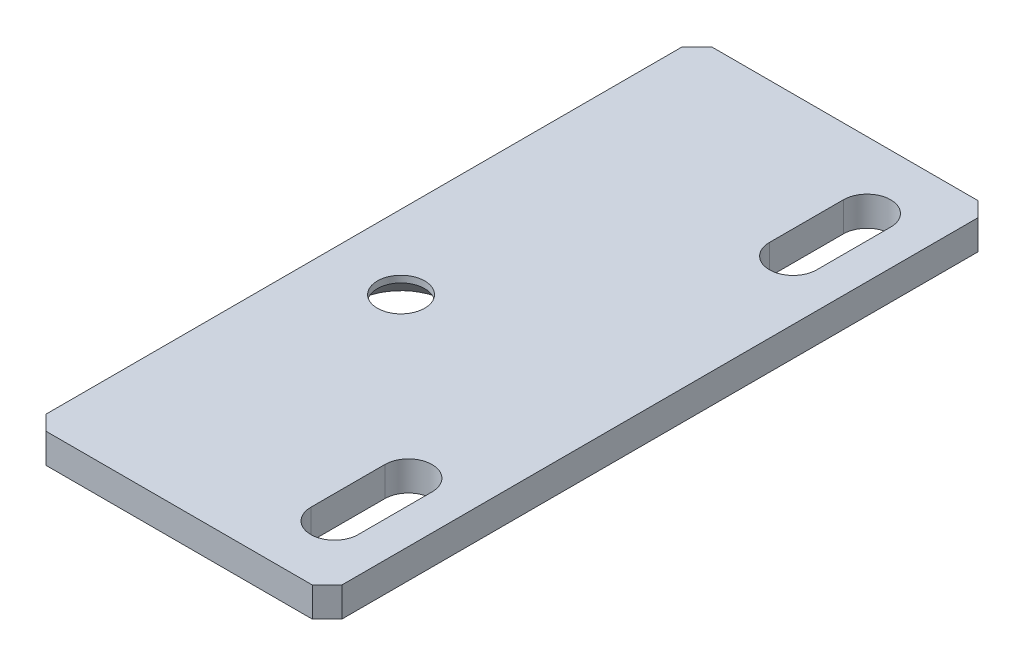
SolidWorks part; units mm, degrees
material "6061 Alloy"
ref_plane "Front Plane" through (0, 0, 0) normal (0, 0, 1) x (1, 0, 0)
ref_plane "Top Plane" through (0, 0, 0) normal (0, 1, 0) x (1, 0, 0)
ref_plane "Right Plane" through (0, 0, 0) normal (1, 0, 0) x (0, 0, -1)
sketch "Sketch1" plane through (0, 0, 0) normal (0, 1, 0) x (1, 0, 0)
  line L5 (10, -22.5) -> (-10, -22.5)
  line L6 (10, -22.5) -> (10, 22.5)
  line L7 (10, 22.5) -> (-10, 22.5)
  line L8 (-10, -22.5) -> (-10, 22.5)
  line L9 (10, -22.5) -> (-10, 22.5) construction
  line L10 (10, 22.5) -> (-10, -22.5) construction
  point P0 (0, 0)
  dimension "D3" = 20
  dimension "D4" = 45
extrude "Base" add sketch "Sketch1" along normal blind 2
sketch "Sketch6" plane through (0, 2, 0) normal (0, 1, 0) x (1, 0, 0)
  line L0 (6, 18) -> (6, 13) construction
  line L1 (7.6, 18) -> (7.6, 13)
  line L2 (4.4, 18) -> (4.4, 13)
  line L3 (6, -13) -> (6, -18) construction
  line L4 (7.6, -13) -> (7.6, -18)
  line L5 (4.4, -13) -> (4.4, -18)
  line L6 (0, 0) -> (-4.8321, 0) construction
  line L7 (10, -22.5) -> (10, 22.5) construction
  line L8 (10, 22.5) -> (-10, 22.5) construction
  arc A0 (7.6, 18) -> (4.4, 18) centre (6, 18) ccw
  arc A1 (4.4, 13) -> (7.6, 13) centre (6, 13) ccw
  arc A2 (7.6, -13) -> (4.4, -13) centre (6, -13) ccw
  arc A3 (4.4, -18) -> (7.6, -18) centre (6, -18) ccw
  point P3 (6, 15.5)
  point P8 (6, -15.5)
  dimension "D1" = 3.2
  dimension "D2" = 5
  dimension "D3" = 31
  dimension "D4" = 4
  dimension "D5" = 4.5
extrude "ScrewSlots" cut sketch "Sketch6" against normal through all
hole_wizard "PulleyHole" positions "Sketch4" profile "Sketch5" countersink size "M3" standard "ANSI Metric" end condition through all
sketch "Sketch4" plane through (0, 0, 0) normal (0, -1, 0) x (-1, 0, 0)
  line L2 (-10, -22.5) -> (-10, 22.5) construction
  line L3 (10, -22.5) -> (-10, -22.5) construction
  point P0 (5, -2.5)
  dimension "D1" = 20
  dimension "D2" = 15
sketch "Sketch5" plane through (-5, 0, 2.5) normal (1, 0, 0) x (0, 0, -1)
  line L0 (0, 0) -> (0, 2)
  line L1 (0, 2) -> (1.6, 2)
  line L2 (1.6, 2) -> (1.6, 1.55)
  line L3 (1.6, 1.55) -> (3.15, 0)
  line L5 (3.15, 0) -> (0, 0)
  line L6 (-1.6, 1.55) -> (-3.15, 0) construction
  line L11 (0, -6.35) -> (0, 107.95) construction
  dimension "Thru Hole Dia." = 3.2
  dimension "Thru Hole Depth" = 2
  dimension "Near C'Sink Dia." = 6.3
  dimension "Near C'Sink Angle" = 90
chamfer "Chamfer1" distance 1 angle 45 4 edges at (-10, 1, -22.5) (10, 1, -22.5) (10, 1, 22.5) (-10, 1, 22.5)
